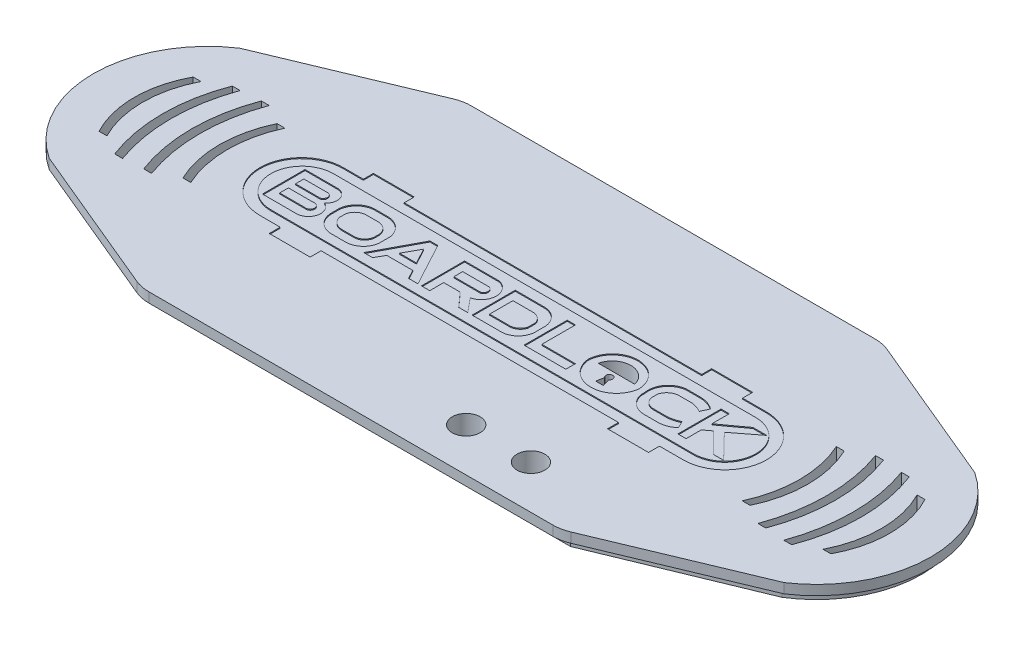
SolidWorks part; units mm, degrees
ref_plane "Front Plane" through (0, 0, 0) normal (0, 0, 1) x (1, 0, 0)
ref_plane "Top Plane" through (0, 0, 0) normal (0, 1, 0) x (1, 0, 0)
ref_plane "Right Plane" through (0, 0, 0) normal (1, 0, 0) x (0, 0, -1)
sketch "Sketch2" plane through (0, 0, 0) normal (0, 1, 0) x (1, 0, 0)
  line L0 (0, 0) -> (102, 0) construction
  line L1 (0, 0) -> (0, -77.2) construction
  line L2 (102, 0) -> (102, -77.2) construction
  line L3 (0, -77.2) -> (102, -77.2) construction
  line L4 (51, 0) -> (51, -77.2) construction
  line L5 (0, -38.6) -> (102, -38.6) construction
  line L6 (-2.5, 2.5) -> (104.5, 2.5)
  line L7 (-2.5, -79.7) -> (104.5, -79.7)
  line L8 (104.5, 2.5) -> (144.7372, -14.2911)
  line L9 (104.5, -79.7) -> (144.7372, -62.9089)
  line L10 (102, -38.6) -> (155.3, -38.6) construction
  line L11 (-2.5, -79.7) -> (-42.7372, -62.9089)
  line L12 (-2.5, 2.5) -> (-42.7372, -14.2911)
  line L13 (0, 0) -> (102, 0)
  line L14 (102, 0) -> (104.5, 0)
  line L15 (104.5, 0) -> (142.7026, -15.7437)
  line L16 (104.5, -77.2) -> (142.7026, -61.4563)
  line L17 (102, -77.2) -> (104.5, -77.2)
  line L18 (-2.5, -77.2) -> (-40.7026, -61.4563)
  line L19 (0, -77.2) -> (-2.5, -77.2)
  line L20 (-2.5, 0) -> (-40.7026, -15.7437)
  line L21 (0, 0) -> (-2.5, 0)
  line L22 (0, -77.2) -> (102, -77.2)
  line L23 (0.5, 0) -> (0.5, -77.2) construction
  line L24 (0, -76.7) -> (97.7329, -76.7) construction
  line L25 (0.5, -74.6) -> (97.3633, -74.6) construction
  line L26 (63.32, -77.2) -> (63.32, 0) construction
  line L27 (0.5, -62.6) -> (97.044, -62.6) construction
  line L28 (75.32, -62.6) -> (75.32, -74.6) construction
  line L29 (79.83, -62.6) -> (79.83, -74.6) construction
  line L30 (91.83, -62.6) -> (91.83, -74.6) construction
  line L31 (69.32, -62.6) -> (69.32, -74.6) construction
  line L32 (63.32, -68.6) -> (75.32, -68.6) construction
  line L33 (85.83, -62.6) -> (85.83, -74.6) construction
  line L34 (79.83, -68.6) -> (91.83, -68.6) construction
  arc A0 (144.7372, -14.2911) -> (144.7372, -62.9089) centre (128.65, -38.6) cw
  arc A1 (-42.7372, -14.2911) -> (-42.7372, -62.9089) centre (-26.65, -38.6) ccw
  arc A2 (142.7026, -15.7437) -> (142.7026, -61.4563) centre (128.65, -38.6) cw
  arc A3 (-40.7026, -15.7437) -> (-40.7026, -61.4563) centre (-26.65, -38.6) ccw
  circle A4 centre (69.32, -68.6) radius 3.55
  circle A5 centre (85.83, -68.6) radius 3.55
  point P16 (157.8, -38.6)
  dimension "D3" = 2.5
  dimension "D10" = 2.5
  dimension "D1" = 77.2
  dimension "D2" = 102
  dimension "D4" = 2.5
  dimension "D5" = 2.5
  dimension "D6" = 2.5
  dimension "D7" = 0.5
  dimension "D8" = 2.5
  dimension "D9" = 53.3
  dimension "D11" = 0.5
  dimension "D12" = 2.1
  dimension "D13" = 62.82
  dimension "D14" = 12
  dimension "D15" = 12
  dimension "D16" = 4.51
  dimension "D17" = 12
  dimension "D18" = 6
  dimension "D19" = 6
  dimension "D20" = 6
  dimension "D21" = 6
extrude "Boss-Extrude3" add sketch "Sketch2" along normal blind 2.5 contours L6 L8 A0 L9 L7 L11 A1 L12
extrude "Boss-Extrude4" add sketch "Sketch2<8>" against normal blind 2.5 contours L20 A3 L18 L19 L22 L17 L16 A2 L15 L14 L13 L21 region at (50.8464, 0, 38.4266)
sketch "Sketch2<8>" plane through (0, 0, 0) normal (0, 1, 0) x (1, 0, 0) same geometry as "Sketch2"
sketch "Sketch3" plane through (0, 2.5, 0) normal (0, 1, 0) x (1, 0, 0)
  line L0 (-55.8, -38.6) -> (157.8, -38.6) construction
  line L1 (51, 2.5) -> (51, -79.7) construction
  line L2 (-2.5, 2.5) -> (104.5, 2.5) construction
  line L3 (-2.5, -79.7) -> (104.5, -79.7) construction
  line L4 (201.4283, 144.6262) -> (1084.095, 144.6262) construction
  line L5 (-2.9873, -27.462) -> (1.9495, -27.462)
  line L6 (1.9495, -27.462) -> (1.9495, -24.9021)
  line L7 (1.9495, -24.9021) -> (12.3717, -24.9021)
  line L8 (12.3717, -24.9021) -> (12.3717, -27.462)
  line L9 (12.3717, -27.462) -> (88.2398, -27.462)
  line L10 (88.2398, -27.462) -> (88.2398, -24.9021)
  line L11 (88.2398, -24.9021) -> (98.6886, -24.9021)
  line L12 (98.6886, -24.9021) -> (98.6886, -27.462)
  line L13 (98.6886, -27.462) -> (104.6245, -27.462)
  line L14 (104.6245, -48.6746) -> (98.6886, -48.6746)
  line L15 (98.6886, -48.6746) -> (98.6886, -51.4646)
  line L16 (98.6886, -51.4646) -> (88.2398, -51.4646)
  line L17 (88.2398, -51.4646) -> (88.2398, -48.6746)
  line L18 (88.2398, -48.6746) -> (12.3717, -48.6746)
  line L19 (12.3717, -48.6746) -> (12.3717, -51.4646)
  line L20 (12.3717, -51.4646) -> (1.9495, -51.4646)
  line L21 (1.9495, -51.4646) -> (1.9495, -48.6746)
  line L22 (1.9495, -48.6746) -> (-2.9873, -48.6746)
  line L23 (-2.9873, -30.0692) -> (104.7002, -30.0692)
  line L24 (104.7002, -46.0158) -> (-3.1948, -46.0158)
  line L25 (-7.6306, -32.7625) -> (-7.6306, -43.6232)
  line L26 (-7.6306, -43.6232) -> (1.1441, -43.6232)
  line L27 (-7.6306, -32.7625) -> (0.7133, -32.7625)
  line L28 (5.3465, -39.2139) -> (5.3465, -36.9174)
  line L29 (-5.6807, -35.0072) -> (0.6, -35.0072)
  line L30 (-5.6807, -35.0072) -> (-5.6807, -37.1385)
  line L31 (-5.6807, -37.1385) -> (0.6, -37.1385)
  line L33 (-5.6807, -38.9524) -> (0.7133, -38.9524)
  line L34 (-5.6807, -38.9524) -> (-5.6807, -41.1744)
  line L35 (-5.6807, -41.1744) -> (0.7133, -41.1744)
  line L41 (10.1371, -35.0072) -> (13.3467, -35.0072)
  line L42 (9.866, -32.6184) -> (13.2281, -32.6184)
  line L43 (18.2229, -43.6232) -> (20.4629, -43.6232)
  line L44 (18.0967, -36.7888) -> (18.0967, -39.563)
  line L45 (16.1379, -37.4286) -> (16.1379, -38.7874)
  line L46 (13.8283, -43.6232) -> (10.2518, -43.6232)
  line L47 (20.4629, -43.6232) -> (21.7662, -41.3167)
  line L48 (13.6087, -41.3167) -> (10.2917, -41.3167)
  line L49 (21.7662, -41.3167) -> (28.4046, -41.3167)
  line L50 (7.3404, -38.9659) -> (7.3404, -37.4286)
  line L51 (28.4046, -41.3167) -> (29.6467, -43.6232)
  line L52 (29.6467, -43.6232) -> (32.0292, -43.6232)
  line L53 (32.0292, -43.6232) -> (26.1026, -32.6184)
  line L54 (26.1026, -32.6184) -> (24.0876, -32.6184)
  line L55 (24.0876, -32.6184) -> (18.2229, -43.6232)
  line L56 (22.9065, -39.2139) -> (27.2439, -39.2139)
  line L57 (27.2439, -39.2139) -> (25.0951, -35.224)
  line L58 (25.0951, -35.224) -> (22.9065, -39.2139)
  line L59 (32.928, -32.6184) -> (32.928, -43.6232)
  line L60 (32.928, -43.6232) -> (35.043, -43.6232)
  line L61 (35.043, -43.6232) -> (35.043, -40.0634)
  line L62 (35.043, -40.0634) -> (39.244, -40.0634)
  line L63 (39.244, -40.0634) -> (42.431, -43.6232)
  line L64 (42.431, -43.6232) -> (44.7378, -43.6232)
  line L65 (44.7378, -43.6232) -> (41.7936, -40.0634)
  line L66 (32.928, -32.6184) -> (41.7936, -32.6184)
  line L67 (35.043, -35.224) -> (35.043, -37.4805)
  line L68 (35.043, -37.4805) -> (41.7936, -37.4805)
  line L69 (35.043, -35.224) -> (41.7936, -35.224)
  line L70 (45.8463, -32.6184) -> (45.8463, -43.6232)
  line L71 (45.8463, -43.6232) -> (52.8329, -43.6232)
  line L72 (45.8463, -32.6184) -> (52.9687, -32.6184)
  line L73 (57.6458, -36.7888) -> (57.6458, -39.563)
  line L74 (47.8647, -35.224) -> (47.8647, -41.1744)
  line L75 (47.8647, -41.1744) -> (52.6, -41.1744)
  line L76 (47.8647, -35.224) -> (52.6, -35.224)
  line L77 (55.6246, -37.1385) -> (55.6246, -39.1866)
  line L78 (59.1096, -32.6184) -> (59.1096, -43.6232)
  line L79 (59.1096, -43.6232) -> (69.7525, -43.6232)
  line L80 (69.7525, -43.6232) -> (69.7525, -41.1876)
  line L81 (69.7525, -41.1876) -> (61.1954, -41.1876)
  line L82 (61.1954, -41.1876) -> (61.1954, -32.6184)
  line L83 (61.1954, -32.6184) -> (59.1096, -32.6184)
  line L84 (72.3273, -37.9056) -> (81.6057, -37.9056)
  line L85 (76.285, -40.2528) -> (75.9572, -42.1923)
  line L86 (75.9572, -42.1923) -> (77.8461, -42.1923)
  line L87 (77.8461, -42.1923) -> (77.3335, -40.2528)
  line L88 (90.3322, -35.0072) -> (93.3549, -35.0072)
  line L89 (96.0824, -35.9398) -> (96.9798, -33.9561)
  line L90 (92.9888, -32.6184) -> (89.5293, -32.6184)
  line L91 (86.9671, -37.333) -> (86.9671, -38.6)
  line L92 (86.9671, -38.6) -> (86.9671, -39.0585)
  line L93 (89.7665, -41.1876) -> (93.2664, -41.1876)
  line L94 (96.1597, -40.3804) -> (97.0399, -42.1923)
  line L95 (93.0498, -43.6232) -> (90.1278, -43.6232)
  line L96 (84.9417, -38.6) -> (84.9417, -39.5139)
  line L97 (98.3461, -32.6195) -> (98.3461, -43.6259)
  line L98 (98.3461, -43.6259) -> (100.4335, -43.6259)
  line L99 (100.4335, -43.6259) -> (100.4335, -39.7387)
  line L100 (100.4335, -39.7387) -> (102.2231, -38.4318)
  line L101 (102.2231, -38.4318) -> (107.3754, -43.6259)
  line L102 (107.3754, -43.6259) -> (110.0073, -43.6259)
  line L103 (110.0073, -43.6259) -> (103.904, -37.333)
  line L104 (103.904, -37.333) -> (110.0073, -32.6195)
  line L105 (110.0073, -32.6195) -> (106.4905, -32.6195)
  line L106 (106.4905, -32.6195) -> (100.4335, -37.0424)
  line L107 (100.4335, -37.0424) -> (100.4335, -32.6195)
  line L108 (100.4335, -32.6195) -> (98.3461, -32.6195)
  arc A0 (86.9671, -37.333) -> (90.3322, -35.0072) centre (90.1278, -38.3088) cw
  arc A1 (93.3549, -35.0072) -> (96.0824, -35.9398) centre (92.5616, -41.7819) cw
  arc A2 (-42.7372, -14.2911) -> (-42.7372, -62.9089) centre (-26.65, -38.6) ccw construction
  arc A3 (144.7372, -62.9089) -> (144.7372, -14.2911) centre (128.65, -38.6) ccw construction
  arc A4 (-2.9873, -27.462) -> (-2.9873, -48.6746) centre (-3.1948, -38.0683) ccw
  arc A5 (104.6245, -27.462) -> (104.6245, -48.6746) centre (104.776, -38.0683) cw
  arc A6 (-2.9873, -30.0692) -> (-3.1948, -46.0158) centre (-3.091, -38.0425) ccw
  arc A7 (104.7002, -30.0692) -> (104.7002, -46.0158) centre (104.7002, -38.0425) cw
  arc A8 (0.7133, -32.7625) -> (2.2325, -37.6827) centre (0.6, -35.492) cw
  arc A9 (1.1441, -43.6232) -> (2.2325, -37.6827) centre (1.0303, -40.5324) ccw
  arc A10 (0.6, -35.0072) -> (0.6, -37.1385) centre (0.3019, -36.0728) cw
  arc A11 (0.7133, -41.1744) -> (0.7133, -38.9524) centre (0.9838, -40.0634) ccw
  arc A12 (5.3465, -36.9174) -> (9.866, -32.6184) centre (10.1371, -37.4286) cw
  arc A13 (18.0967, -36.7888) -> (13.2281, -32.6184) centre (13.2836, -37.4805) ccw
  arc A14 (5.3465, -39.2139) -> (10.2518, -43.6232) centre (10.0037, -38.9659) ccw
  arc A15 (13.8283, -43.6232) -> (18.0967, -39.563) centre (13.6087, -39.1187) ccw
  arc A16 (10.1371, -35.0072) -> (7.3404, -37.4286) centre (10.2483, -37.9613) ccw
  arc A17 (13.3467, -35.0072) -> (16.1379, -37.4286) centre (13.2781, -37.9056) cw
  arc A18 (16.1379, -38.7874) -> (13.6087, -41.3167) centre (13.3904, -38.5692) cw
  arc A19 (10.2917, -41.3167) -> (7.3404, -38.9659) centre (10.2917, -38.2887) cw
  arc A20 (41.7936, -35.224) -> (41.7936, -37.4805) centre (41.488, -36.3523) cw
  arc A21 (41.7936, -40.0634) -> (41.7936, -32.6184) centre (40.9073, -36.3409) ccw
  arc A22 (52.9687, -32.6184) -> (57.6458, -36.7888) centre (53.222, -37.0421) cw
  arc A23 (57.6458, -39.563) -> (52.8329, -43.6232) centre (53.2093, -39.1866) cw
  arc A24 (52.6, -35.224) -> (55.6246, -37.1385) centre (52.8789, -38.1299) cw
  arc A25 (55.6246, -39.1866) -> (52.6, -41.1744) centre (52.8755, -38.2986) cw
  arc A26 (70.3877, -38.6) -> (83.4404, -38.6) centre (76.9141, -38.8997) cw
  arc A27 (70.3877, -38.6) -> (83.4404, -38.6) centre (76.9141, -37.8504) ccw
  arc A28 (76.285, -40.2528) -> (77.3335, -40.2528) centre (76.8092, -39.581) cw
  arc A29 (72.3273, -37.9056) -> (81.6057, -37.9056) centre (76.9665, -38.9919) cw
  arc A30 (96.9798, -33.9561) -> (92.9888, -32.6184) centre (93.0498, -39.0585) ccw
  arc A31 (89.5293, -32.6184) -> (84.9417, -38.6) centre (89.9999, -37.7293) ccw
  arc A32 (86.9671, -39.0585) -> (89.7665, -41.1876) centre (89.6538, -38.4308) ccw
  arc A33 (93.2664, -41.1876) -> (96.1597, -40.3804) centre (92.4973, -32.8415) ccw
  arc A34 (84.9417, -39.5139) -> (90.1278, -43.6232) centre (89.7907, -38.7214) ccw
  arc A35 (93.0498, -43.6232) -> (97.0399, -42.1923) centre (93.1901, -37.7354) ccw
extrude "Logo" cut sketch "Sketch3" against normal blind 0.25 contours L26 A9 A8 L27 L25 A11 L35 L34 L33 L29 A10 L31 L30 | L46 A15 L44 A13 L42 A12 L28 A14 L48 A19 L50 A16 L41 A17 L45 A18 | L54 L55 L43 L47 L49 L51 L52 L53 L58 L57 L56 | L65 A21 L66 L59 L60 L61 L62 L63 L64 L69 A20 L68 L67 | A23 L73 A22 L72 L70 L71 L77 A25 L75 L74 L76 A24 | A26 A27 L85 A28 L87 L86 L84 A29 | L95 A35 L94 A33 L93 A32 L92 L91 A0 L88 A1 L89 A30 L90 A31 L96 A34 | L107 L108 L97 L98 L99 L100 L101 L102 L103 L104 L105 L106 | L82 L83 L78 L79 L80 L81 | A4 L22 L21 L20 L19 L18 L17 L16 L15 L14 A5 L13 L12 L11 L10 L9 L8 L7 L6 L5 | A6 L24 A7 L23 | L78 L79 L80 L81 L82 L83 region at (-2.2321, 2.5, 38.3038) region at (5.5149, 2.5, 38.0657) region at (21.3111, 2.5, 38.2038) region at (37.3608, 2.5, 32.7798) region at (49.4075, 2.5, 32.7799) region at (60.1525, 2.5, 32.7715) region at (88.1536, 2.5, 35.4525) region at (102.8661, 2.5, 37.8921) region at (76.9141, 2.5, 32.5442)
fillet "Fillet1" radius 10 4 edges at (-2.5, 1.25, -2.5) (104.5, 1.25, -2.5) (104.5, 1.25, 79.7) (-2.5, 1.25, 79.7)
sketch "Sketch4" plane through (0, 2.5, 0) normal (0, 1, 0) x (1, 0, 0)
  line L0 (-55.8, -38.6) -> (157.8, -38.6) construction
  line L1 (51, 2.5) -> (51, -79.7) construction
  line L2 (-0.4972, 2.5) -> (102.4972, 2.5) construction
  line L3 (-0.4972, -79.7) -> (102.4972, -79.7) construction
  line L4 (-42.3364, -26.6) -> (-42.3364, -50.6) construction
  line L5 (-40.3364, -26.6) -> (-40.3364, -50.6) construction
  line L6 (-35.3364, -23.6) -> (-35.3364, -53.6) construction
  line L7 (-33.3364, -23.6) -> (-33.3364, -53.6) construction
  line L8 (-28.3364, -23.2) -> (-28.3364, -53.2) construction
  line L9 (-26.3364, -23.2) -> (-26.3364, -53.2) construction
  line L10 (-21.3364, -26.2) -> (-21.3364, -50.2) construction
  line L11 (-19.3364, -26.2) -> (-19.3364, -50.2) construction
  line L12 (-42.3364, -26.6) -> (-40.3364, -26.6)
  line L13 (-42.3364, -50.6) -> (-40.3364, -50.6)
  line L14 (-35.3364, -53.6) -> (-33.3364, -53.6)
  line L15 (-35.3364, -23.6) -> (-33.3364, -23.6)
  line L16 (-28.3364, -23.2) -> (-26.3364, -23.2)
  line L17 (-28.3364, -53.2) -> (-26.3364, -53.2)
  line L18 (-21.3364, -50.2) -> (-19.3364, -50.2)
  line L19 (-21.3364, -26.2) -> (-19.3364, -26.2)
  line L20 (121.3364, -26.2) -> (121.3364, -50.2) construction
  line L21 (123.3364, -26.2) -> (123.3364, -50.2) construction
  line L22 (128.3364, -23.2) -> (128.3364, -53.2) construction
  line L23 (130.3364, -23.2) -> (130.3364, -53.2) construction
  line L24 (135.3364, -23.6) -> (135.3364, -53.6) construction
  line L25 (137.3364, -23.6) -> (137.3364, -53.6) construction
  line L26 (142.3364, -26.6) -> (142.3364, -50.6) construction
  line L27 (144.3364, -26.6) -> (144.3364, -50.6) construction
  line L28 (123.3364, -26.2) -> (121.3364, -26.2)
  line L29 (123.3364, -50.2) -> (121.3364, -50.2)
  line L30 (130.3364, -53.2) -> (128.3364, -53.2)
  line L31 (130.3364, -23.2) -> (128.3364, -23.2)
  line L32 (137.3364, -23.6) -> (135.3364, -23.6)
  line L33 (137.3364, -53.6) -> (135.3364, -53.6)
  line L34 (144.3364, -50.6) -> (142.3364, -50.6)
  line L35 (144.3364, -26.6) -> (142.3364, -26.6)
  arc A0 (-42.7372, -14.2911) -> (-42.7372, -62.9089) centre (-26.65, -38.6) ccw construction
  arc A1 (144.7372, -62.9089) -> (144.7372, -14.2911) centre (128.65, -38.6) ccw construction
  arc A2 (-42.3364, -26.6) -> (-42.3364, -50.6) centre (-19.91, -38.6) ccw
  arc A3 (-40.3364, -26.6) -> (-40.3364, -50.6) centre (-16.7181, -38.6) ccw
  arc A4 (-35.3364, -23.6) -> (-35.3364, -53.6) centre (3.8054, -38.6) ccw
  arc A5 (-33.3364, -53.6) -> (-33.3364, -23.6) centre (8.2465, -38.6) cw
  arc A6 (-28.3364, -23.2) -> (-28.3364, -53.2) centre (11.3609, -38.2) ccw
  arc A7 (-26.3364, -23.2) -> (-26.3364, -53.2) centre (14.8909, -38.2) ccw
  arc A8 (-21.3364, -26.2) -> (-21.3364, -50.2) centre (3.9499, -38.2) ccw
  arc A9 (-19.3364, -26.2) -> (-19.3364, -50.2) centre (6.9686, -38.2) ccw
  arc A10 (121.3364, -26.2) -> (121.3364, -50.2) centre (95.0314, -38.2) cw
  arc A11 (123.3364, -26.2) -> (123.3364, -50.2) centre (98.0501, -38.2) cw
  arc A12 (128.3364, -23.2) -> (128.3364, -53.2) centre (87.1091, -38.2) cw
  arc A13 (130.3364, -23.2) -> (130.3364, -53.2) centre (90.6391, -38.2) cw
  arc A14 (135.3364, -53.6) -> (135.3364, -23.6) centre (93.7535, -38.6) ccw
  arc A15 (137.3364, -23.6) -> (137.3364, -53.6) centre (98.1946, -38.6) cw
  arc A16 (142.3364, -26.6) -> (142.3364, -50.6) centre (118.7181, -38.6) cw
  arc A17 (144.3364, -26.6) -> (144.3364, -50.6) centre (121.91, -38.6) cw
  dimension "D1" = 24
  dimension "D2" = 12
  dimension "D3" = 30
  dimension "D4" = 15
  dimension "D5" = 2
  dimension "D6" = 2
  dimension "D7" = 2
  dimension "D8" = 2
  dimension "D9" = 7
  dimension "D10" = 7
  dimension "D11" = 7
extrude "SoundGaps" cut sketch "Sketch4" against normal up to next
sketch "Sketch5" plane through (0, 2.5, 0) normal (0, 1, 0) x (1, 0, 0)
  circle A2 centre (69.32, -68.6) radius 3.55
  circle A3 centre (85.83, -68.6) radius 3.55
extrude "Buttons" cut sketch "Sketch5" against normal up to next
extrude "Cut-Extrude5" cut sketch "Sketch3<5>" against normal up to next contours A29 L84 | L85 L86 L87 A28 region at (76.9665, 2.5, 36.3712)
sketch "Sketch3<5>" plane through (0, 2.5, 0) normal (0, 1, 0) x (1, 0, 0) same geometry as "Sketch3"
